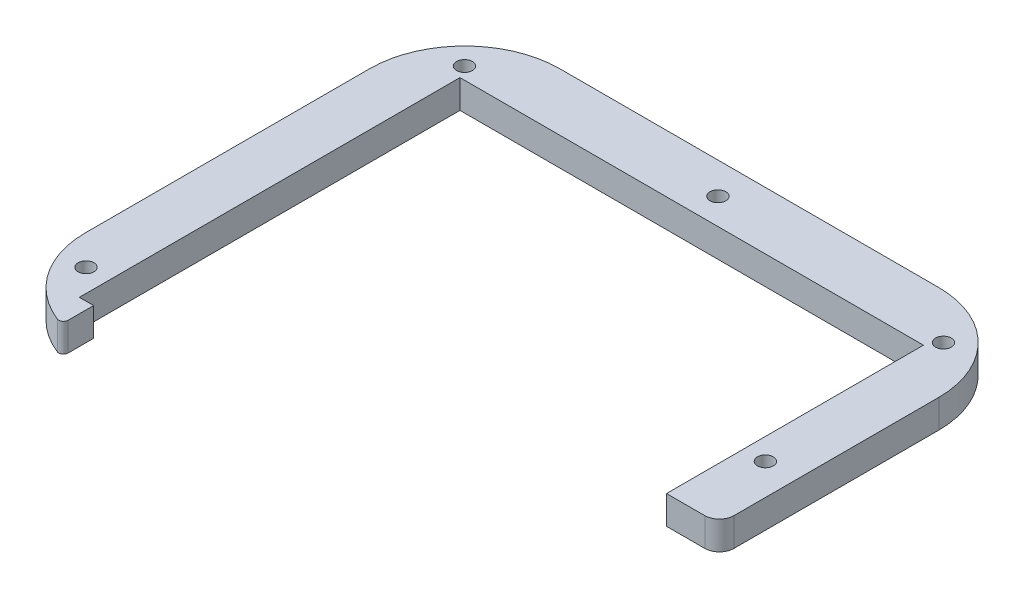
SolidWorks part; units mm, degrees
ref_plane "Front Plane" through (0, 0, 0) normal (0, 0, 1) x (1, 0, 0)
ref_plane "Top Plane" through (0, 0, 0) normal (0, 1, 0) x (1, 0, 0)
ref_plane "Right Plane" through (0, 0, 0) normal (1, 0, 0) x (0, 0, -1)
sketch "Sketch1" plane through (0, 0, 0) normal (0, 1, 0) x (1, 0, 0)
  line L0 (-60, 30) -> (-60, -30)
  line L1 (-40, 50) -> (40, 50)
  line L2 (-40, -50) -> (40, -50)
  line L3 (0, 50) -> (0, -50) construction
  line L4 (-60, 0) -> (94.7381, 0) construction
  line L5 (60, 0) -> (-94.7381, 0) construction
  line L6 (60, 30) -> (60, -30)
  arc A0 (-40, 50) -> (-60, 30) centre (-40, 30) ccw
  arc A1 (-40, -50) -> (-60, -30) centre (-40, -30) cw
  arc A2 (40, -50) -> (60, -30) centre (40, -30) ccw
  arc A3 (40, 50) -> (60, 30) centre (40, 30) cw
  dimension "D1" = 20
  dimension "D2" = 120
  dimension "D3" = 100
extrude "Boss-Extrude1" add sketch "Sketch1" along normal blind 6
sketch "Sketch2" plane through (0, 6, 0) normal (0, 1, 0) x (1, 0, 0)
  line L0 (0, 38) -> (0, -50) construction
  line L1 (-49, 38) -> (49, 38)
  line L2 (-49, 38) -> (-49, -50) construction
  line L3 (-49, -50) -> (49, -50) construction
  line L4 (49, 38) -> (49, -50)
  line L5 (-40, -50) -> (40, -50) construction
  line L6 (-49, -42.5) -> (-46, -42.5)
  line L7 (-46, -42.5) -> (-46, -50)
  line L8 (-49, -42.5) -> (-49, 38)
  line L9 (-46, -50) -> (49, -50)
  dimension "D1" = 98
  dimension "D2" = 88
  dimension "D3" = 3
  dimension "D4" = 7.5
extrude "Cut-Extrude1" cut sketch "Sketch2" against normal through all
sketch "Sketch3" plane through (0, 6, 0) normal (0, 1, 0) x (1, 0, 0)
  line L0 (49, -47.8606) -> (49, 38) construction
  line L1 (49, -16.24) -> (74, -16.24)
  line L2 (49, -16.24) -> (49, -47.8606)
  line L3 (49, -47.8606) -> (74, -47.8606)
  line L4 (74, -16.24) -> (74, -47.8606)
  line L5 (40, 50) -> (-40, 50) construction
  dimension "D1" = 66.24
  dimension "D2" = 25
extrude "Cut-Extrude2" cut sketch "Sketch3" against normal through all
fillet "Fillet1" radius 3 1 edges at (60, 3, 16.24)
sketch "Sketch4" plane through (0, 6, 0) normal (0, 1, 0) x (1, 0, 0)
  line L0 (50.5586, 40.5086) -> (0, 0) construction
  line L1 (-50.5586, 40.5086) -> (0, 0) construction
  line L3 (0, 0) -> (-53.7093, -36.2274) construction
  line L6 (0, 0) -> (-60, 0) construction
  line L7 (-60, 30) -> (-60, -30) construction
  circle A1 centre (53.475, 0) radius 1.75
  circle A2 centre (-53.7093, -36.2274) radius 1.75
  circle A4 centre (0, 43.45) radius 1.75
  circle A7 centre (50.5586, 40.5086) radius 1.75
  circle A8 centre (-50.5586, 40.5086) radius 1.75
  dimension "D1" = 3.5
  dimension "D2" = 141.298
  dimension "D3" = 53.475
  dimension "D4" = 43.45
  dimension "D5" = 64.7851
  dimension "D6" = 38.702
  dimension "D7" = 34
  dimension "D8" = 64.7851
  dimension "D9" = 64.7851
extrude "Cut-Extrude3" cut sketch "Sketch4" against normal through all
other "Move Face1" face at (-49, 3, 2.25) face at (-49, 3, 2.25) face at (-47.5, 3, 42.5) face at (-46, 3, 45.7894) face at (-53.7093, 0, 37.9774) face at (0, 3, -38) face at (49, 3, -10.88) face at (53, 3, 16.24) face at (58.8107, 3, 15.0507) face at (60, 3, -8.38) face at (52.0711, 3, -42.0711) face at (0, 3, -50) face at (-52.0711, 3, -42.0711) face at (-60, 3, 0) face at (-54.5623, 3, 40.6858) face at (-50.5586, 0, -42.2586) face at (50.5586, 0, -38.7586) face at (0, 0, -41.7) face at (53.475, 0, 1.75) offset 0.08 parameters "D1"=0.08
fillet "Fillet2" radius 1 1 edges at (-45.92, 3, 49.1875)
